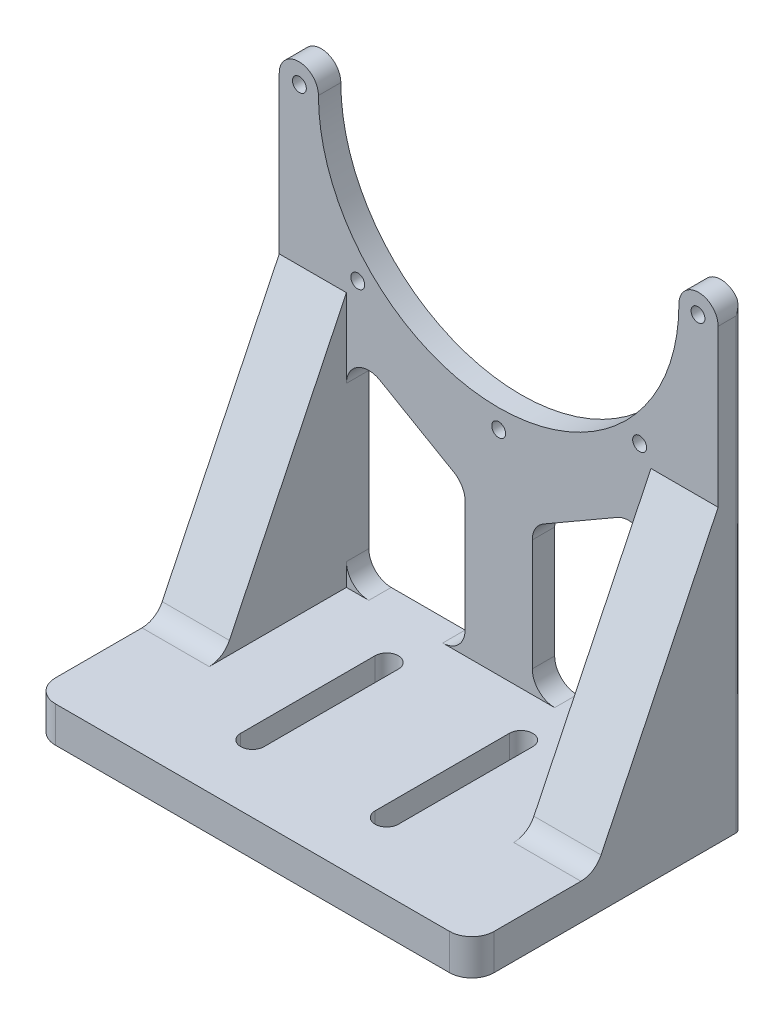
SolidWorks part; units mm, degrees
ref_plane "Front Plane" through (0, 0, 0) normal (0, 0, 1) x (1, 0, 0)
ref_plane "Top Plane" through (0, 0, 0) normal (0, 1, 0) x (1, 0, 0)
ref_plane "Right Plane" through (0, 0, 0) normal (1, 0, 0) x (0, 0, -1)
sketch "Sketch1" plane through (0, 0, 0) normal (0, 0, 1) x (1, 0, 0)
  line L0 (0, 0) -> (0, -85) construction
  line L1 (-49, 0) -> (-49, -100)
  line L2 (-49, -100) -> (49, -100)
  line L3 (49, -100) -> (49, 0)
  line L4 (-49, -92) -> (49, -92) construction
  line L5 (-12.5, -92) -> (-29, -92)
  line L6 (-34, -87) -> (-34, -43.8786)
  line L8 (-7.5, -87) -> (-7.5, -62.0652)
  line L9 (-10, -57.735) -> (-34, -43.8786)
  line L10 (10, -57.735) -> (34, -43.8786)
  line L11 (7.5, -87) -> (7.5, -62.0652)
  line L12 (34, -87) -> (34, -43.8786)
  line L13 (12.5, -92) -> (29, -92)
  circle A0 centre (0, 0) radius 40.25 construction
  circle A1 centre (0, 0) radius 49 construction
  circle A2 centre (0, 0) radius 44.5 construction
  circle A3 centre (0, -44.5) radius 1.55
  circle A4 centre (-31.4663, -31.4663) radius 1.55
  circle A5 centre (-44.5, 0) radius 1.55
  circle A6 centre (-31.4663, 31.4663) radius 1.55 [skipped]
  circle A7 centre (0, 44.5) radius 1.55 [skipped]
  circle A8 centre (31.4663, 31.4663) radius 1.55 [skipped]
  circle A9 centre (44.5, 0) radius 1.55
  circle A10 centre (31.4663, -31.4663) radius 1.55
  arc A11 (-40.25, 0) -> (40.25, 0) centre (0, 0) ccw
  arc A12 (-40.25, 0) -> (-49, 0) centre (-44.625, 0) ccw
  arc A13 (40.25, 0) -> (49, 0) centre (44.625, 0) cw
  arc A14 (-29, -92) -> (-34, -87) centre (-29, -87) cw
  arc A15 (-12.5, -92) -> (-7.5, -87) centre (-12.5, -87) ccw
  arc A16 (-7.5, -62.0652) -> (-10, -57.735) centre (-12.5, -62.0652) ccw
  arc A19 (7.5, -62.0652) -> (10, -57.735) centre (12.5, -62.0652) cw
  arc A20 (12.5, -92) -> (7.5, -87) centre (12.5, -87) cw
  arc A21 (29, -92) -> (34, -87) centre (29, -87) ccw
  point P25 (0, 0)
  point P36 (-34, -47.152)
  point P37 (-13.1456, -70.5045)
  point P39 (-7.5, -71.2778)
  point P40 (-7.5, -63.6997)
  dimension "D1" = 98
  dimension "D2" = 80.5
  dimension "D3" = 89
  dimension "D5" = 3.1
  dimension "D7" = 100
  dimension "D13" = 5
  dimension "D4" = 85
  dimension "D8" = 8
  dimension "D9" = 15
  dimension "D10" = 7.5
  dimension "D11" = 55
  dimension "D12" = 60
  dimension "D6" = 8
extrude "Boss-Extrude1" add sketch "Sketch1" along normal blind 5
sketch "Sketch2" plane through (0, 0, 5) normal (0, 0, 1) x (1, 0, 0)
  line L1 (-49, -100) -> (49, -100)
  line L2 (-49, -100) -> (-49, -92)
  line L3 (-49, -92) -> (49, -92)
  line L4 (49, -100) -> (49, -92)
extrude "Boss-Extrude2" add sketch "Sketch2" along normal blind 55
sketch "Sketch3" plane through (49, 0, 0) normal (1, 0, 0) x (0, 0, -1)
  line L0 (-5, 0) -> (-5, -35) construction
  line L1 (-5, -92) -> (-5, 0) construction
  line L2 (-5, -35) -> (-32.5, -92)
  line L3 (-60, -92) -> (-5, -92) construction
  line L4 (-32.5, -92) -> (-5, -92)
  line L5 (-5, -92) -> (-5, -35)
  dimension "D1" = 35
extrude "Boss-Extrude3" add sketch "Sketch3" against normal blind 15
mirror "Mirror1" about plane through (0, 0, 0) normal (1, 0, 0) of "Boss-Extrude3"
fillet "Fillet2" radius 5 6 edges at (34, -43.8786, 2.5) (41.5, -92, 32.5) (-49, -96, 60) (49, -96, 60) (-41.5, -92, 32.5) (-34, -43.8786, 2.5)
sketch "Sketch4" plane through (0, -92, 0) normal (0, 1, 0) x (1, 0, 0)
  line L0 (0, -60) -> (0, 0) construction
  line L1 (44, -60) -> (-44, -60) construction
  line L2 (-15, -45) -> (-15, -15) construction
  line L3 (-17.6, -45) -> (-17.6, -15)
  line L4 (-12.4, -45) -> (-12.4, -15)
  line L5 (15, -45) -> (15, -15) construction
  line L6 (17.6, -45) -> (17.6, -15)
  line L7 (12.4, -45) -> (12.4, -15)
  arc A0 (-17.6, -45) -> (-12.4, -45) centre (-15, -45) ccw
  arc A1 (-12.4, -15) -> (-17.6, -15) centre (-15, -15) ccw
  arc A2 (17.6, -45) -> (12.4, -45) centre (15, -45) cw
  arc A3 (12.4, -15) -> (17.6, -15) centre (15, -15) cw
  point P7 (-15, -30)
  point P12 (-15, -28.7424)
  point P15 (15, -30)
  dimension "D1" = 2.6
  dimension "D2" = 30
  dimension "D3" = 15
  dimension "D4" = 15
extrude "Cut-Extrude1" cut sketch "Sketch4" against normal blind 15
fillet "Fillet3" radius 1 2 edges at (49, -50, 0) (-49, -50, 0) tangent propagation no
